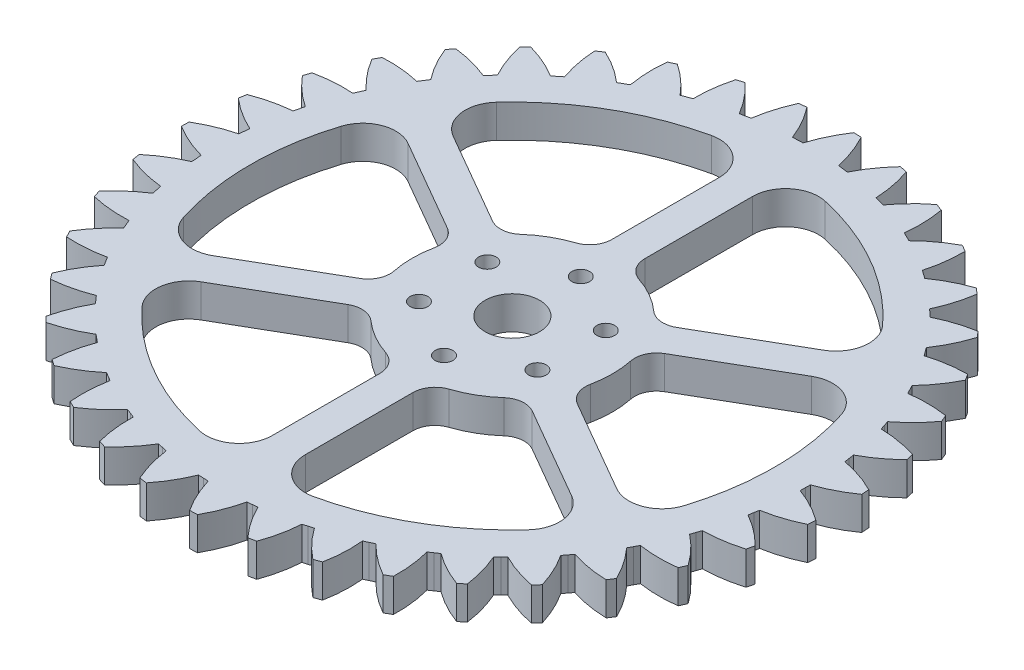
SolidWorks part; units mm, degrees
ref_plane "Front Plane" through (0, 0, 0) normal (0, 0, 1) x (1, 0, 0)
ref_plane "Top Plane" through (0, 0, 0) normal (0, 1, 0) x (1, 0, 0)
ref_plane "Right Plane" through (0, 0, 0) normal (1, 0, 0) x (0, 0, -1)
sketch "Sketch1" plane through (0, 0, 0) normal (0, 1, 0) x (1, 0, 0)
  line L6 (-7, -4.0415) -> (0, -8.0829)
  line L7 (0, -8.0829) -> (7, -4.0415)
  line L8 (7, -4.0415) -> (7, 4.0415)
  line L9 (7, 4.0415) -> (0, 8.0829)
  line L10 (0, 8.0829) -> (-7, 4.0415)
  line L11 (-7, 4.0415) -> (-7, -4.0415)
  line L12 (-7, -4.0415) -> (0, -8.0829)
  line L13 (0, -8.0829) -> (7, -4.0415)
  line L14 (7, -4.0415) -> (7, 4.0415)
  line L15 (7, 4.0415) -> (0, 8.0829)
  line L16 (0, 8.0829) -> (-7, 4.0415)
  line L17 (-7, 4.0415) -> (-7, -4.0415)
  circle A0 centre (0, 0) radius 28.4436 construction
  circle A1 centre (0, 0) radius 28.4436
  circle A3 centre (-5.3694, 3.1) radius 0.8
  circle A4 centre (-5.3694, 3.1) radius 0.8
  circle A5 centre (0, 0) radius 2.475
  circle A6 centre (0, 0) radius 2.475
  circle A7 centre (-5.3694, -3.1) radius 0.8
  circle A8 centre (-5.3694, -3.1) radius 0.8
  circle A9 centre (0, -6.2) radius 0.8
  circle A10 centre (0, -6.2) radius 0.8
  circle A11 centre (5.3694, -3.1) radius 0.8
  circle A12 centre (5.3694, -3.1) radius 0.8
  circle A13 centre (5.3694, 3.1) radius 0.8
  circle A14 centre (5.3694, 3.1) radius 0.8
  circle A15 centre (0, 6.2) radius 0.8
  circle A16 centre (0, 6.2) radius 0.8
  dimension "D1" = 0
  dimension "D2" = 0
  dimension "D3" = 0
  dimension "D4" = 0
  dimension "D5" = 0
  dimension "D6" = 0
  dimension "D7" = 0
  dimension "D8" = 0
sketch "Sketch2"
sketch "Sketch5" plane through (0, 0, 0) normal (0, 1, 0) x (1, 0, 0)
  line L0 (0, 0) -> (29.8198, 2.1775) construction
  line L1 (29.8449, 1.834) -> (29.7947, 2.5211) construction
  line L2 (29.7947, 2.5211) -> (29.8198, 2.1775)
  line L3 (0, 0) -> (26.45, 4.0908)
  line L4 (26.45, 4.0908) -> (26.5209, 3.6382)
  line L5 (26.4813, 3.8882) -> (26.4186, 4.2934) construction
  line L6 (29.8449, 1.834) -> (29.8198, 2.1775)
  line L7 (26.7636, -0.205) -> (26.7681, 0.253)
  line L8 (0, 0) -> (26.7636, -0.205)
  arc A0 (26.5209, 3.6382) -> (29.7947, 2.5211) centre (24.2901, -8.2545) cw
  arc A1 (26.7681, 0.253) -> (29.8449, 1.834) centre (22.8333, 11.6956) ccw
  dimension "D1" = 4.615
extrude "Boss-Extrude1" add sketch "Sketch5" along normal blind 1.5 and the other way blind 1.5
pattern_circular "CirPattern2" count 39 over 360 about axis through (0, -1.5, 0) along (0, 1, 0) of "Boss-Extrude1"
sketch "Sketch3" plane through (0, 1.5, 0) normal (0, 1, 0) x (1, 0, 0)
  circle A0 centre (-5.3694, 3.1) radius 0.8 construction
  circle A1 centre (-5.3694, -3.1) radius 0.8 construction
  circle A2 centre (0, -6.2) radius 0.8 construction
  circle A3 centre (5.3694, -3.1) radius 0.8 construction
  circle A4 centre (5.3694, 3.1) radius 0.8 construction
  circle A5 centre (0, 6.2) radius 0.8 construction
  circle A6 centre (-5.3694, 3.1) radius 0.8
  circle A7 centre (-5.3694, -3.1) radius 0.8
  circle A8 centre (0, -6.2) radius 0.8
  circle A9 centre (5.3694, -3.1) radius 0.8
  circle A10 centre (5.3694, 3.1) radius 0.8
  circle A11 centre (0, 6.2) radius 0.8
  circle A12 centre (0, 0) radius 2.475 construction
  circle A13 centre (0, 0) radius 2.475
extrude "Cut-Extrude1" cut sketch "Sketch3" against normal through all
sketch "Sketch4" plane through (0, 1.5, 0) normal (0, 1, 0) x (1, 0, 0)
  line L0 (0, 0) -> (43301.2702, 25000) construction
  line L1 (-1000, 0) -> (49000, 0) construction
  line L2 (8.508, 3.1801) -> (21.2896, 10.5595)
  line L3 (8.508, -3.1801) -> (21.2896, -10.5595)
  line L4 (26.7621, -0.4101) -> (26.7652, 0) construction
  circle A0 centre (0, 0) radius 2.475 construction
  circle A1 centre (0, 0) radius 8.0829 construction
  circle A2 centre (0, 0) radius 26.7644 construction
  circle A4 centre (0, 0) radius 9.0829 construction
  arc A5 (8.508, 3.1801) -> (8.508, -3.1801) centre (0, 0) cw
  arc A6 (21.2896, 10.5595) -> (21.2896, -10.5595) centre (0, 0) cw
  circle A7 centre (0, 0) radius 23.7644 construction
  dimension "D3" = 1.5
  dimension "D1" = 3
  dimension "D2" = 1
extrude "Cut-Extrude2" cut sketch "Sketch4" against normal through all
fillet "Fillet1" radius 3 2 edges at (21.2896, 0, 10.5595) (21.2896, 0, -10.5595)
fillet "Fillet2" radius 2 2 edges at (8.508, 0, 3.1801) (8.508, 0, -3.1801)
pattern_circular "CirPattern1" count 6 over 360 about axis through (0, -1.5, 0) along (0, 1, 0) of "Cut-Extrude2", "Fillet1", "Fillet2" reverse direction yes
